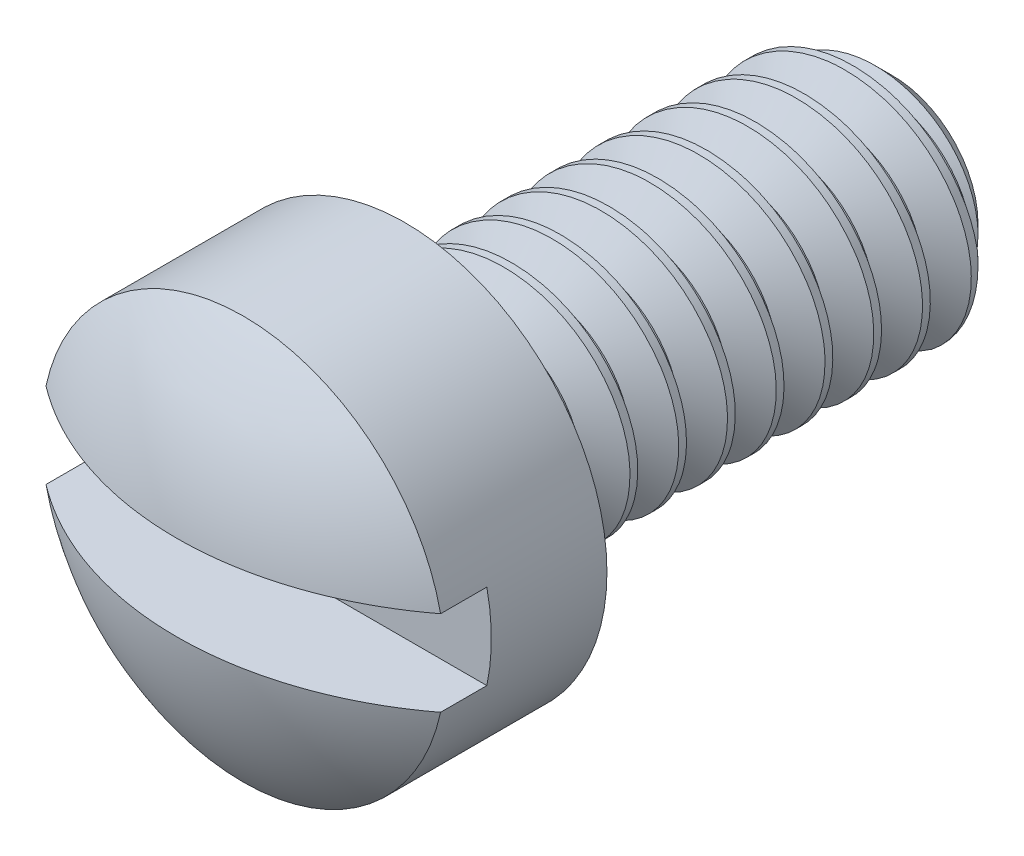
SolidWorks part; units mm, degrees
ref_plane "Front" through (0, 0, 0) normal (0, 0, 1) x (1, 0, 0)
ref_plane "Top" through (0, 0, 0) normal (0, 1, 0) x (1, 0, 0)
ref_plane "Right" through (0, 0, 0) normal (1, 0, 0) x (0, 0, -1)
sketch "Sketch1" plane through (0, 0, 0) normal (0, 0, 1) x (1, 0, 0)
  circle A0 centre (0, 0) radius 5.2578
  dimension "Head Dia" = 10.5156
extrude "Extrude3" add sketch "Sketch1" along normal blind 6.0198
sketch "Sketch11" plane through (0, 0, 0) normal (1, 0, 0) x (0, 0, -1)
  line L0 (0, 0) -> (-6.2738, 0) construction
  line L4 (-6.0198, 5.2578) -> (-6.0198, -5.2578) construction
  line L5 (-6.2738, 5.4681) -> (0, 5.4681)
  line L7 (0, 5.4681) -> (0, 5.2578)
  line L8 (-4.2139, 5.2578) -> (0, 5.2578)
  line L9 (0, -5.2578) -> (0, 5.2578) construction
  line L13 (-6.0198, 0) -> (-6.2738, 0)
  line L14 (-6.2738, 0) -> (-6.2738, 5.4681)
  arc A0 (-4.2139, 5.2578) -> (-6.0198, 0) centre (2.5369, 0) ccw
  dimension "D3" = 0.254
  dimension "D5" = 0.2103
  dimension "D2" = 1.8059
revolve "Cut-Revolve3" cut sketch "Sketch11" angle 360 about L0
sketch "Sketch4" plane through (0, 0, 0) normal (1, 0, 0) x (0, 0, -1)
  line L0 (0, 0) -> (12.7, 0)
  line L3 (12.7, 0) -> (12.7, 3.175)
  line L4 (12.7, 3.175) -> (0, 3.175)
  line L6 (0, 3.175) -> (0, 0)
  line L9 (12.7, 3.175) -> (12.7, -3.175) construction
  dimension "length" = 12.7
  dimension "dia" = 6.35
revolve "Revolve1" add sketch "Sketch4" angle 360 about L0
sketch "Sketch13" plane through (0, 0, -12.7) normal (0, 0, -1) x (-1, 0, 0)
  circle A2 centre (0, 0) radius 3.175
curve "Helix/Spiral1" pitch 1.27 height 18.7198 radius 3.175 centre (0, 0, -12.7) axis (0, 0, 1) start towards (1, 0, 0)
chamfer "Chamfer2" distance 0.9525 angle 45 1 edges at (3.175, 0, -12.7)
sketch "Sketch14" plane through (0, 0, 0) normal (1, 0, 0) x (0, 0, -1)
  line L0 (12.7, 3.2147) -> (13.8113, 3.2147)
  line L1 (13.8113, 3.2147) -> (13.335, 2.3555)
  line L2 (13.335, 2.3555) -> (13.1763, 2.3555)
  line L3 (13.1763, 2.3555) -> (12.7, 3.2147)
  line L4 (12.9381, 2.7851) -> (13.5731, 2.7851) construction
  dimension "D1" = 0.1588
  dimension "D2" = 58
  dimension "D3" = 0.635
  dimension "D4" = 0.0397
sweep "Cut-Sweep1" cut profiles "Sketch14" path "Helix/Spiral1" align with end faces yes
ref_plane "Plane1" through (0, 0, 25.4) normal (0, 0, -1) x (-1, 0, 0)
sketch "Sketch29" [suppressed] plane through (0, 0, 28.575) normal (0, 0, -1) x (-1, 0, 0)
  circle A0 centre (0, 0) radius 1.7526 construction
  circle A1 centre (0, 0) radius 1.7526
  point P3 (0, -1.7526)
  point P4 (0, 1.7526)
extrude "Extrude11" [suppressed] add sketch "Sketch29" against normal up to surface (28.575 mm away) up to plane "Front"
ref_plane "Plane2" through (0, 0, 6.0198) normal (0, 0, 1) x (1, 0, 0)
sketch "Sketch26" plane through (0, 0, 0) normal (0, 0, 1) x (1, 0, 0)
  circle A1 centre (0, 0) radius 0.5461
  dimension "D1" = 1.0922
extrude "Extrude13" add sketch "Sketch26" along normal up to surface (6.0024 mm away)
sketch "Sketch31" plane through (0, 0, 6.0198) normal (0, 0, 1) x (1, 0, 0)
  line L0 (-5.2578, 1.1113) -> (5.2578, -1.1112) construction
  line L1 (-5.2578, 1.1113) -> (5.2578, 1.1113)
  line L2 (-5.2578, 1.1113) -> (-5.2578, -1.1113)
  line L3 (-5.2578, -1.1113) -> (5.2578, -1.1112)
  line L4 (5.2578, 1.1113) -> (5.2578, -1.1112)
  circle A0 centre (0, 0) radius 5.2578 construction
  dimension "D1" = 2.2225
extrude "Extrude15" cut sketch "Sketch31" against normal blind 3.0099
sketch "Sketch18" plane through (0, 0, 0) normal (1, 0, 0) x (0, 0, -1)
  line L1 (12.7, 3.175) -> (0, 3.175) construction
  point P0 (10.795, -3.175)
  point P1 (11.43, 3.175)
  point P2 (-6.0198, 1.1113)
  dimension "D1" = 1.27
  dimension "D2" = 1.905
equation "\"D3@Helix/Spiral1\" = \"length@Sketch4\" + \"Head Ht@Extrude3\""
equation "\"D1@Sketch14\" = \"D4@Helix/Spiral1\" * .125"
equation "\"D3@Sketch14\" = \"D4@Helix/Spiral1\" * .5"
equation "\"D5@Sketch11\" = \"Head Dia@Sketch1\" * .02"
equation "\"D4@Sketch14\" = \"D1@Sketch14\" * .25"
equation "\"D1@Chamfer2\" = \"D4@Helix/Spiral1\" * .75"
equation "\"D1@Sketch18\" = \"D4@Helix/Spiral1\""
equation "\"D2@Sketch18\" = \"D4@Helix/Spiral1\" * 1.5"
equation "\"D1@Extrude15\" = \"Head Ht@Extrude3\" * .5"
equation "\"D2@Sketch11\" = \"Head Ht@Extrude3\" * .3"
equation "\"D1@Sketch31\" = \"D4@Helix/Spiral1\" * 1.75"
